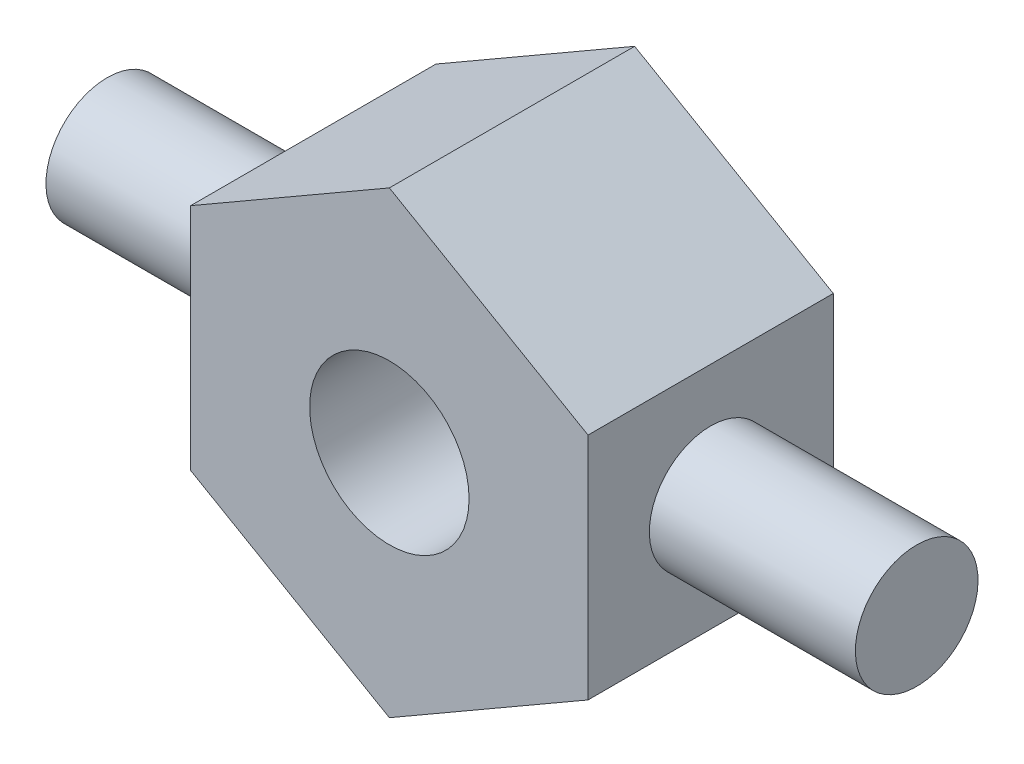
SolidWorks part; units mm, degrees
ref_plane "Front Plane" through (0, 0, 0) normal (0, 0, 1) x (1, 0, 0)
ref_plane "Top Plane" through (0, 0, 0) normal (0, 1, 0) x (1, 0, 0)
ref_plane "Right Plane" through (0, 0, 0) normal (1, 0, 0) x (0, 0, -1)
sketch "Sketch1" plane through (0, 0, 0) normal (0, 0, 1) x (1, 0, 0)
  line L1 (0, -93.5307) -> (81, -46.7654)
  line L2 (81, -46.7654) -> (81, 46.7654)
  line L3 (81, 46.7654) -> (0, 93.5307)
  line L4 (0, 93.5307) -> (-81, 46.7654)
  line L5 (-81, 46.7654) -> (-81, -46.7654)
  line L6 (-81, -46.7654) -> (0, -93.5307)
  dimension "D1" = 162
extrude "Boss-Extrude2" add sketch "Sketch1" along normal blind 50 and the other way blind 50
sketch "Sketch4" plane through (0, 0, 0) normal (0, 0, 1) x (1, 0, 0)
  line L0 (165, 0) -> (-165, 0) construction
  line L1 (-165, 0) -> (-165, 25)
  line L2 (-165, 25) -> (165, 25)
  line L3 (165, 25) -> (165, 0)
  line L4 (81, -46.7654) -> (81, 46.7654) construction
  line L5 (165, 0) -> (-165, 0)
  dimension "D1" = 25
  dimension "D2" = 330
  dimension "D3" = 84
revolve "Revolve2" add sketch "Sketch4" angle 360 about L0
sketch "Sketch5" plane through (0, 0, 50) normal (0, 0, 1) x (1, 0, 0)
  circle A0 centre (0, 0) radius 32.5
extrude "Cut-Extrude1" cut sketch "Sketch5" against normal through all
cosmetic thread "Cosmetic Thread2" parameters "D2"=75.19
